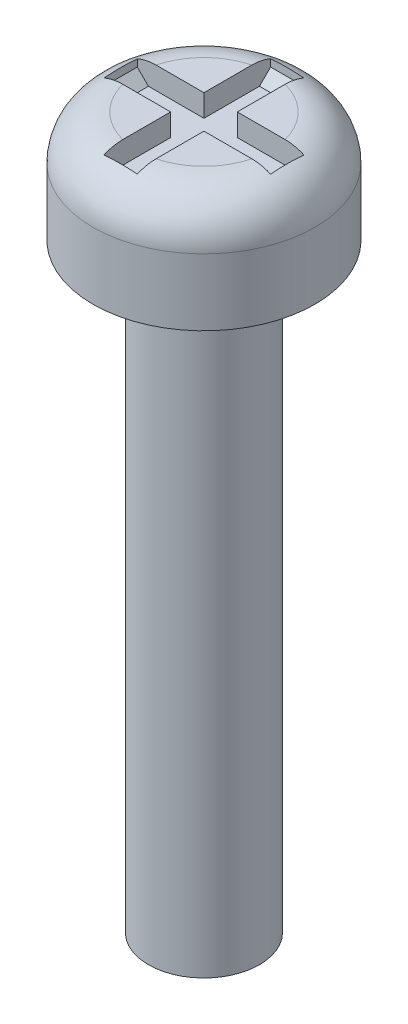
SolidWorks part; units mm, degrees
ref_plane "Front Plane" through (0, 0, 0) normal (0, 0, 1) x (1, 0, 0)
ref_plane "Top Plane" through (0, 0, 0) normal (0, 1, 0) x (1, 0, 0)
ref_plane "Right Plane" through (0, 0, 0) normal (1, 0, 0) x (0, 0, -1)
sketch "Sketch1" plane through (0, 0, 0) normal (0, 1, 0) x (1, 0, 0)
  circle A0 centre (0, 0) radius 2
  dimension "D1" = 4
extrude "Boss-Extrude1" add sketch "Sketch1" along normal blind 2
fillet "Fillet1" radius 0.8 1 edges at (0, 2, 2)
sketch "Sketch2" plane through (0, 2, 0) normal (0, 1, 0) x (1, 0, 0)
  line L1 (-1.5, 0.3) -> (1.5, 0.3)
  line L2 (-1.5, 0.3) -> (-1.5, -0.3)
  line L3 (-1.5, -0.3) -> (1.5, -0.3)
  line L4 (1.5, 0.3) -> (1.5, -0.3)
  line L5 (-1.5, 0.3) -> (1.5, -0.3) construction
  line L6 (-1.5, -0.3) -> (1.5, 0.3) construction
  line L7 (-0.3, -1.5) -> (0.3, -1.5)
  line L8 (-0.3, -1.5) -> (-0.3, 1.5)
  line L9 (-0.3, 1.5) -> (0.3, 1.5)
  line L10 (0.3, -1.5) -> (0.3, 1.5)
  line L11 (-0.3, -1.5) -> (0.3, 1.5) construction
  line L12 (-0.3, 1.5) -> (0.3, -1.5) construction
  point P0 (0, 0)
  point P6 (0, 0)
  circle M9 centre (0, 0) radius 1.2
  dimension "D1" = 1.5
  dimension "D2" = 0.6
extrude "Cut-Extrude1" cut sketch "Sketch2" against normal blind 0.4 contours L3 L8 L1 M9 | L1 L10 L8 M9 | L2 L3 L1 M9 | L10 L9 L8 M9 | L10 L3 L1 M9 | L4 L1 L3 M9 | L3 L10 L1 L8 | L10 L3 L8 M9 | L7 L10 L8 M9 region at (-1.3435, 2, 0) region at (-0.7438, 2, 0) region at (0, 2, -0.7438) region at (0, 2, 0) region at (0, 2, -1.3435) region at (0.7438, 2, 0) region at (0, 2, 0.7438) region at (0, 2, 1.3435) region at (1.3435, 2, 0)
chamfer "Chamfer1" distance 0.2 angle 45 4 edges at (0, 1.6, 1.5) (1.5, 1.6, 0) (-1.5, 1.6, 0) (0, 1.6, -1.5)
sketch "Sketch3" plane through (0, 0, 0) normal (0, -1, 0) x (1, 0, 0)
  circle A0 centre (0, 0) radius 1
  dimension "D1" = 2
extrude "Boss-Extrude2" add sketch "Sketch3" along normal blind 10.8
